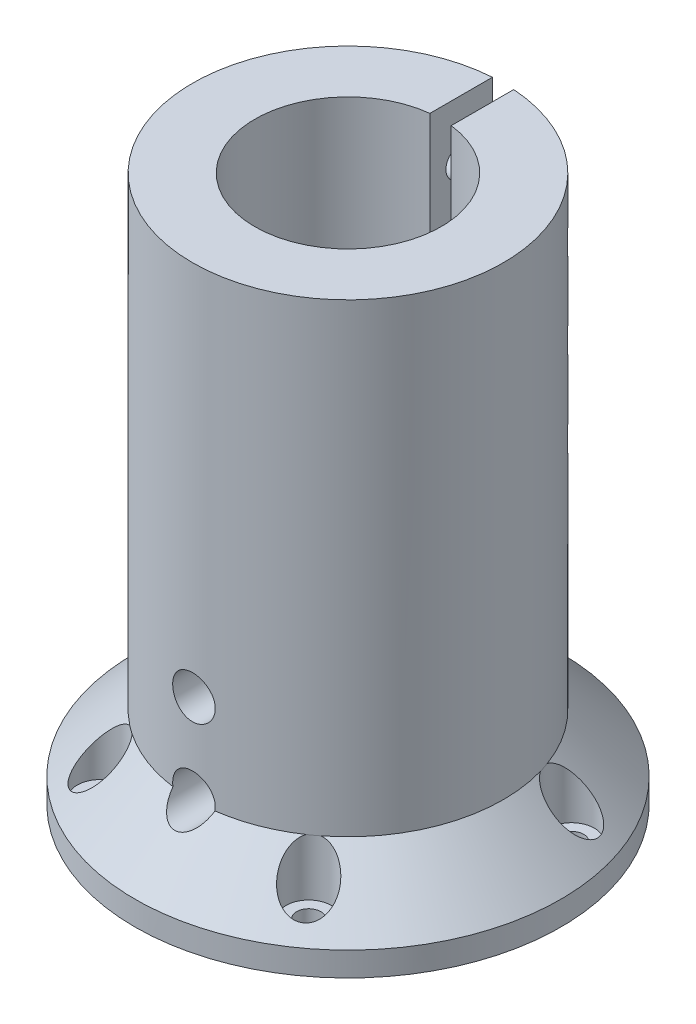
SolidWorks part; units mm, degrees
ref_plane "Front Plane" through (0, 0, 0) normal (0, 0, 1) x (1, 0, 0)
ref_plane "Top Plane" through (0, 0, 0) normal (0, 1, 0) x (1, 0, 0)
ref_plane "Right Plane" through (0, 0, 0) normal (1, 0, 0) x (0, 0, -1)
sketch "Sketch1" plane through (0, 0, 0) normal (0, 1, 0) x (1, 0, 0)
  circle A0 centre (0, 0) radius 25 construction
  circle A1 centre (0, 25) radius 1.7
  circle A2 centre (23.7764, 7.7254) radius 1.7
  circle A3 centre (14.6946, -20.2254) radius 1.7
  circle A4 centre (-14.6946, -20.2254) radius 1.7
  circle A5 centre (-23.7764, 7.7254) radius 1.7
  circle A6 centre (0, 0) radius 30
  circle A7 centre (0, 0) radius 17.5
  point P16 (0, 0)
  dimension "D1" = 50
  dimension "D2" = 3.4
  dimension "D4" = 60
  dimension "D5" = 35
  dimension "D3" = 5
extrude "Boss-Extrude1" add sketch "Sketch1" along normal blind 3
sketch "Sketch2" plane through (0, 3, 0) normal (0, 1, 0) x (1, 0, 0)
  circle A0 centre (0, 25) radius 3.1 construction
  circle A1 centre (0, 0) radius 21.9
  circle A2 centre (0, 0) radius 17.5 construction
  circle A3 centre (0, 0) radius 17.5
  dimension "D1" = 6.2
extrude "Boss-Extrude2" add sketch "Sketch2" along normal blind 32 from surface starting at face at (0, 0, 30)
chamfer "Chamfer1" distance 8.5 angle 45 1 edges at (0, 3, 21.9)
ref_plane "Plane1" through (0, 11.5, 0) normal (0, -1, 0) x (-1, 0, 0)
sketch "Sketch3" plane through (0, 11.5, 0) normal (0, -1, 0) x (-1, 0, 0)
  circle A0 centre (0, 25) radius 1.7 construction
  circle A1 centre (0, 25) radius 1.7
  circle A2 centre (0, 25) radius 3.2
  circle A3 centre (23.7764, 7.7254) radius 3.2
  circle A4 centre (14.6946, -20.2254) radius 3.2
  circle A5 centre (-14.6946, -20.2254) radius 3.2
  circle A6 centre (-23.7764, 7.7254) radius 3.2
  circle A7 centre (-23.7764, 7.7254) radius 1.7 construction
  circle A8 centre (-14.6946, -20.2254) radius 1.7 construction
  circle A9 centre (14.6946, -20.2254) radius 1.7 construction
  circle A10 centre (23.7764, 7.7254) radius 1.7 construction
  circle A11 centre (-23.7764, 7.7254) radius 1.7
  circle A12 centre (-14.6946, -20.2254) radius 1.7
  circle A13 centre (14.6946, -20.2254) radius 1.7
  circle A14 centre (23.7764, 7.7254) radius 1.7
  point P15 (0, 0)
  dimension "D2" = 5
  dimension "D1" = 1.5
extrude "Cut-Extrude3" cut sketch "Sketch3" along normal blind 8
sketch "Sketch4" plane through (0, 0, 0) normal (0, 0, 1) x (1, 0, 0)
  line L0 (0, 12) -> (0, 0) construction
  line L1 (0, 0) -> (0, 24) construction
  circle A0 centre (0, 12) radius 3
  circle A1 centre (0, 24) radius 3
  dimension "D1" = 6
  dimension "D3" = 24
  dimension "D2" = 12
extrude "Cut-Extrude4" cut sketch "Sketch4" along normal through all
sketch "Sketch5" plane through (0, 32, 0) normal (0, 1, 0) x (1, 0, 0)
  circle A0 centre (0, 0) radius 13.125
  circle A1 centre (0, 0) radius 21.9 construction
  circle A2 centre (0, 0) radius 21.9
  dimension "D1" = 26.25
extrude "Boss-Extrude3" add sketch "Sketch5" along normal blind 45
chamfer "Chamfer2" distance 4.5 angle 45 1 edges at (0, 32, 17.5)
sketch "Sketch6" plane through (0, 77, 0) normal (0, 1, 0) x (1, 0, 0)
  line L0 (0, 13.125) -> (0, 0) construction
  line L1 (-1.5, 4.35) -> (1.5, 4.35)
  line L2 (-1.5, 4.35) -> (-1.5, 21.9)
  line L3 (-1.5, 21.9) -> (1.5, 21.9)
  line L4 (1.5, 4.35) -> (1.5, 21.9)
  line L5 (-1.5, 4.35) -> (1.5, 21.9) construction
  line L6 (-1.5, 21.9) -> (1.5, 4.35) construction
  circle A0 centre (0, 0) radius 13.125 construction
  circle A1 centre (0, 0) radius 21.9 construction
  point P0 (0, 13.125)
  dimension "D1" = 3
extrude "Cut-Extrude5" cut sketch "Sketch6" against normal blind 40
sketch "Sketch8" plane through (-1.5, 0, 0) normal (1, 0, 0) x (0, 0, -1)
  line L0 (17.4438, 77) -> (17.4438, 37) construction
  line L4 (21.8486, 77) -> (13.039, 77)
  line L5 (13.039, 77) -> (13.039, 37)
  line L6 (13.039, 37) -> (21.8486, 37)
  line L7 (21.8486, 37) -> (21.8486, 77)
  line L8 (21.8486, 77) -> (13.039, 77) construction
  line L9 (13.039, 77) -> (13.039, 37) construction
  line L10 (13.039, 37) -> (21.8486, 37) construction
  line L11 (21.8486, 37) -> (21.8486, 77) construction
  circle A0 centre (17.4438, 57) radius 2.15
  circle A1 centre (17.4438, 69) radius 2.15
  circle A2 centre (17.4438, 45) radius 2.15
  dimension "D2" = 4.3
  dimension "D3" = 12
  dimension "D4" = 12
  dimension "D1" = 0
extrude "Cut-Extrude6" cut sketch "Sketch8" against normal through all
sketch "Sketch9" plane through (-1.5, 0, 0) normal (1, 0, 0) x (0, 0, -1)
  circle A0 centre (17.4438, 45) radius 2.15 construction
  circle A1 centre (17.4438, 57) radius 2.15 construction
  circle A2 centre (17.4438, 69) radius 2.15 construction
  circle A21 centre (17.4438, 45) radius 2.15 construction
  circle A22 centre (17.4438, 57) radius 2.15 construction
  circle A23 centre (17.4438, 69) radius 2.15 construction
  circle A24 centre (17.4438, 45) radius 3.15
  circle A25 centre (17.4438, 57) radius 3.15
  circle A26 centre (17.4438, 69) radius 3.15
  dimension "D1" = 1
extrude "Cut-Extrude7" cut sketch "Sketch9" along normal blind 10 from offset 16 offset against normal yes
sketch "Sketch10" plane through (1.5, 0, 0) normal (-1, 0, 0) x (0, 0, 1)
  circle A0 centre (-17.4438, 45) radius 2.15 construction
  circle A1 centre (-17.4438, 57) radius 2.15 construction
  circle A2 centre (-17.4438, 69) radius 2.15 construction
  circle A3 centre (-17.4438, 45) radius 2.15 construction
  circle A4 centre (-17.4438, 57) radius 2.15 construction
  circle A5 centre (-17.4438, 69) radius 2.15 construction
  circle A6 centre (-17.4438, 45) radius 1.75
  circle A7 centre (-17.4438, 57) radius 1.75
  circle A8 centre (-17.4438, 69) radius 1.75
  dimension "D1" = 0.4
extrude "Cut-Extrude8" cut sketch "Sketch10" against normal through all
sketch "Sketch11" plane through (1.5, 0, 0) normal (-1, 0, 0) x (0, 0, 1)
  circle A0 centre (-17.4438, 45) radius 1.75 construction
  circle A1 centre (-17.4438, 57) radius 1.75 construction
  circle A2 centre (-17.4438, 69) radius 1.75 construction
  circle A3 centre (-17.4438, 45) radius 1.75 construction
  circle A4 centre (-17.4438, 57) radius 1.75 construction
  circle A5 centre (-17.4438, 69) radius 1.75 construction
  circle A6 centre (-17.4438, 45) radius 3
  circle A7 centre (-17.4438, 57) radius 3
  circle A8 centre (-17.4438, 69) radius 3
  dimension "D1" = 1.25
extrude "Cut-Extrude9" cut sketch "Sketch11" along normal blind 14 from offset 20 offset against normal yes
